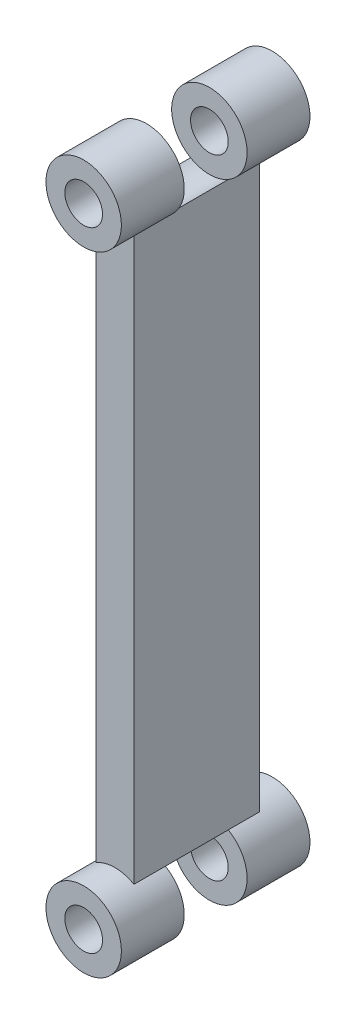
SolidWorks part; units mm, degrees
ref_plane "Alzado" through (0, 0, 0) normal (0, 0, 1) x (1, 0, 0)
ref_plane "Planta" through (0, 0, 0) normal (0, 1, 0) x (1, 0, 0)
ref_plane "Vista lateral" through (0, 0, 0) normal (1, 0, 0) x (0, 0, -1)
sketch "Croquis1" plane through (0, 0, 0) normal (0, 0, 1) x (1, 0, 0)
  line L1 (1.5, -25) -> (-1.5, -25)
  line L2 (1.5, -25) -> (1.5, 25)
  line L3 (1.5, 25) -> (-1.5, 25)
  line L4 (-1.5, -25) -> (-1.5, 25)
  line L5 (1.5, -25) -> (-1.5, 25) construction
  line L6 (1.5, 25) -> (-1.5, -25) construction
  circle A0 centre (0, 25) radius 1.5
  circle A1 centre (0, -25) radius 1.5
  circle A2 centre (0, 25) radius 3
  circle A3 centre (0, -25) radius 3
  point P1 (0, 0)
  dimension "D3" = 6
  dimension "D4" = 6
  dimension "D1" = 3
  dimension "D2" = 50
extrude "Saliente-Extruir1" add sketch "Croquis1" along normal blind 5 and the other way blind 5 contours L3 L4 L1 L2
extrude "Saliente-Extruir3" add sketch "Croquis1<4>" along normal blind 7.5 and the other way blind 7.5 contours A1 | A3 | A0 | A2
sketch "Croquis1<4>" plane through (0, 0, 0) normal (0, 0, 1) x (1, 0, 0) same geometry as "Croquis1"
extrude "Cortar-Extruir1" cut sketch "Croquis1<5>" against normal blind 2.5 and the other way blind 2.5 contours A2 | A3
sketch "Croquis1<5>" plane through (0, 0, 0) normal (0, 0, 1) x (1, 0, 0) same geometry as "Croquis1"
extrude "Cortar-Extruir2" cut sketch "Croquis1<6>" against normal blind 10 and the other way blind 10 contours A1 | A0
sketch "Croquis1<6>" plane through (0, 0, 0) normal (0, 0, 1) x (1, 0, 0) same geometry as "Croquis1"
